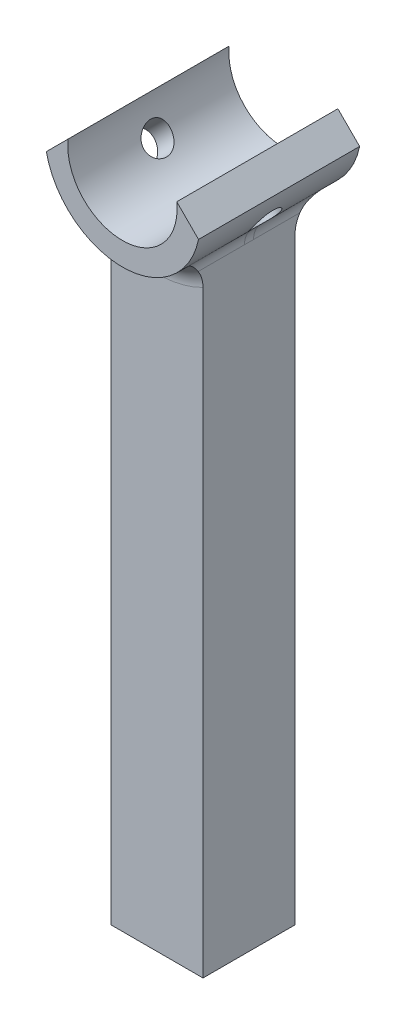
SolidWorks part; units mm, degrees
ref_plane "Front Plane" through (0, 0, 0) normal (0, 0, 1) x (1, 0, 0)
ref_plane "Top Plane" through (0, 0, 0) normal (0, 1, 0) x (1, 0, 0)
ref_plane "Right Plane" through (0, 0, 0) normal (1, 0, 0) x (0, 0, -1)
sketch "Sketch1" plane through (0, 0, 0) normal (0, 1, 0) x (1, 0, 0)
  line L1 (4, -15) -> (-4, -15)
  line L2 (4, -15) -> (4, -7)
  line L3 (4, -7) -> (-4, -7)
  line L4 (-4, -15) -> (-4, -7)
  point P4 (0, -7)
  dimension "D3" = 8
  dimension "D4" = 8
extrude "Boss-Extrude1" add sketch "Sketch1" against normal blind 55 contours L2 L3 L4 L1
sketch "Sketch2" plane through (0, 0, 0) normal (0, 0, 1) x (1, 0, 0)
  line L0 (-3.6183, 0) -> (3.4011, 0) construction
  line L1 (-8, 2) -> (8, 2) construction
  line L2 (-8, 2) -> (-4.4083, 5.5917)
  line L3 (8, 2) -> (3.6742, 6.3258)
  circle A0 centre (0, 4.75) radius 4.75
  circle A1 centre (0, 4.75) radius 6.75
  point P2 (-0.1086, 0)
  dimension "D1" = 0
  dimension "D3" = 2
  dimension "D4" = 45
  dimension "D5" = 45
  dimension "D6" = 8
  dimension "D7" = 8
  dimension "D2" = 2
extrude "Boss-Extrude2" add sketch "Sketch2" along normal blind 3 and the other way blind 11 from surface contours L2 A1 L3 A0 region at (-5.5591, 4.2274, 0) starting at face at (0, -27.5, 15)
ref_plane "Plane1" through (5, 5, 0) normal (0.7071, 0.7071, 0) x (0.7071, -0.7071, 0)
ref_plane "Plane2" through (-5.6066, -5.6066, 0) normal (-0.7071, -0.7071, 0) x (0.7071, -0.7071, 0)
sketch "Sketch4" plane through (-5.6066, -5.6066, 0) normal (-0.7071, -0.7071, 0) x (0.7071, -0.7071, 0)
  line L0 (-2.3425, 7) -> (-2.3425, 15) construction
  circle A0 centre (-4.3425, 11) radius 1.25
  point P4 (-2.3425, 11)
  point P5 (0, 0)
  dimension "D1" = 2
  dimension "D2" = 2.5
extrude "Cut-Extrude1" cut sketch "Sketch4" against normal through all
mirror "Mirror1" about plane through (0, 0, 0) normal (1, 0, 0) of "Cut-Extrude1"
fillet "Fillet1" radius 2 4 edges at (-4, -0.6871, 11) (0, -2, 7) (4, -0.6871, 11) (0, -2, 15)
